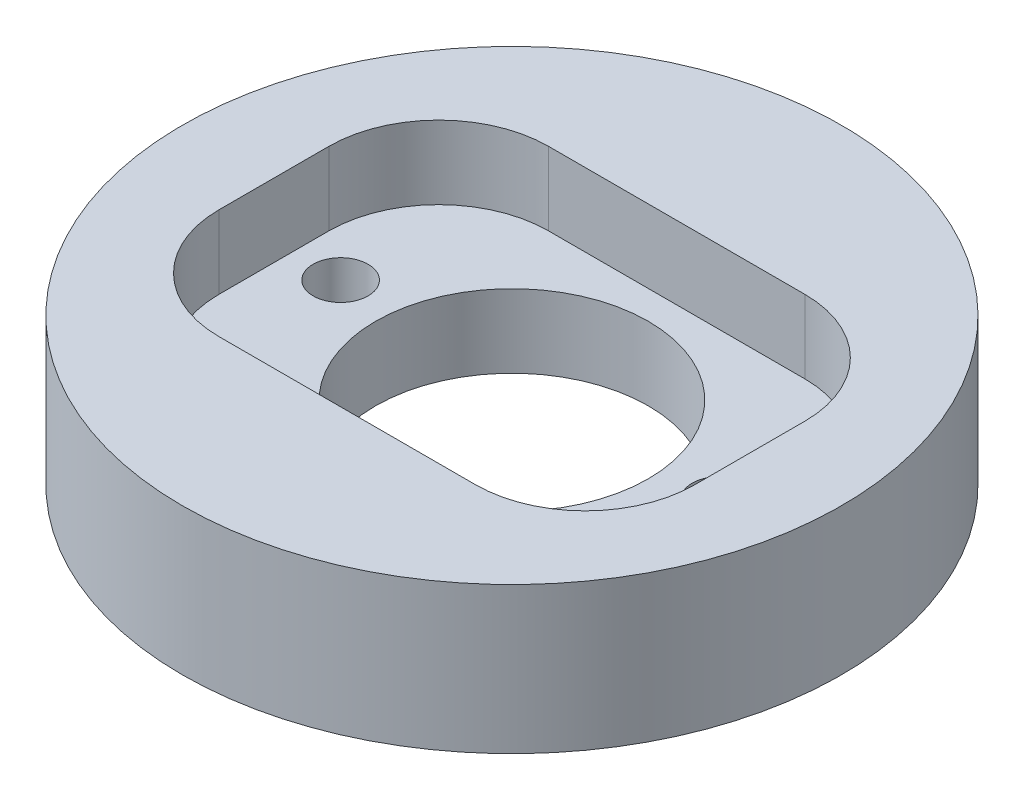
SolidWorks part; units mm, degrees
ref_plane "Front Plane" through (0, 0, 0) normal (0, 0, 1) x (1, 0, 0)
ref_plane "Top Plane" through (0, 0, 0) normal (0, 1, 0) x (1, 0, 0)
ref_plane "Right Plane" through (0, 0, 0) normal (1, 0, 0) x (0, 0, -1)
sketch "Sketch2" plane through (0, 0, 0) normal (0, 1, 0) x (1, 0, 0)
  line L0 (0, 9) -> (0, -22.3339) construction
  line L1 (9, 0) -> (-25.2541, 0) construction
  circle A0 centre (0, 0) radius 9
  dimension "D1" = 18
extrude "Boss-Extrude1" add sketch "Sketch2" along normal blind 4
sketch "Sketch3" plane through (0, 4, 0) normal (0, 1, 0) x (1, 0, 0)
  line L1 (-6.5, 4.5) -> (6.5, 4.5)
  line L2 (-6.5, 4.5) -> (-6.5, -4.5)
  line L3 (-6.5, -4.5) -> (6.5, -4.5)
  line L4 (6.5, 4.5) -> (6.5, -4.5)
  line L5 (-6.5, 4.5) -> (6.5, -4.5) construction
  line L6 (-6.5, -4.5) -> (6.5, 4.5) construction
  point P0 (0, 0)
  dimension "D1" = 13
  dimension "D2" = 9
extrude "Cut-Extrude1" cut sketch "Sketch3" against normal blind 2
fillet "Fillet1" radius 3 4 edges at (-6.5, 3, 4.5) (6.5, 3, 4.5) (-6.5, 3, -4.5) (6.5, 3, -4.5)
sketch "Sketch4" plane through (0, 2, 0) normal (0, 1, 0) x (1, 0, 0)
  line L1 (3.5, 4.5) -> (-3.5, 4.5) construction
  line L2 (0, 0) -> (0, -17.7909) construction
  circle A0 centre (0, 0) radius 3.725
  circle A2 centre (-5.1761, 0.4977) radius 0.75
  circle A3 centre (5.1761, 0.4977) radius 0.75
  dimension "D1" = 7.45
  dimension "D2" = 5.2
  dimension "D3" = 4.5
extrude "Cut-Extrude2" cut sketch "Sketch4" against normal through all
